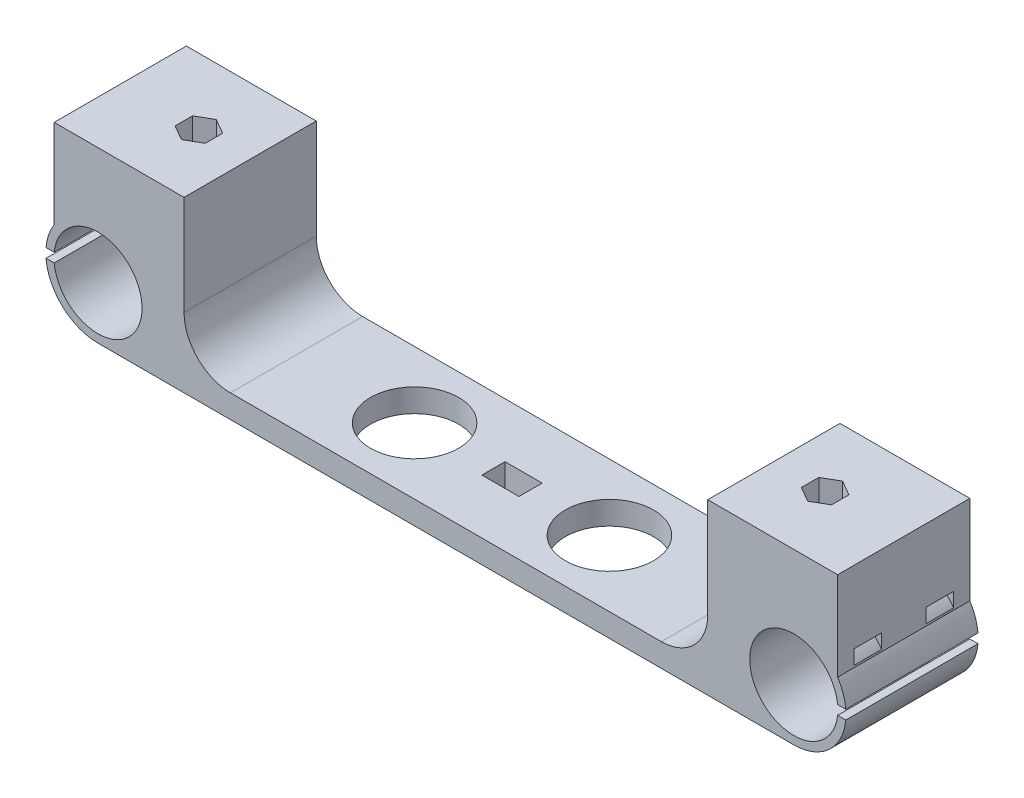
SolidWorks part; units mm, degrees
ref_plane "Front Plane" through (0, 0, 0) normal (0, 0, 1) x (1, 0, 0)
ref_plane "Top Plane" through (0, 0, 0) normal (0, 1, 0) x (1, 0, 0)
ref_plane "Right Plane" through (0, 0, 0) normal (1, 0, 0) x (0, 0, -1)
sketch "Sketch7" plane through (0, 0, 0) normal (0, 0, 1) x (1, 0, 0)
  line L0 (-35.0092, -3.4353) -> (114.9908, -3.4353)
  line L1 (-16.4565, 1.5647) -> (96.438, 1.5647)
  line L8 (126.1962, 6.8147) -> (124.438, 6.8147)
  line L9 (126.1962, 8.8147) -> (124.438, 8.8147)
  line L10 (39.9908, -3.4353) -> (39.9908, 54.826) construction
  line L11 (-46.2147, 8.8147) -> (-44.4565, 8.8147)
  line L12 (-46.2147, 6.8147) -> (-44.4565, 6.8147)
  line L19 (-44.4565, 13.9231) -> (-44.4565, 33.0647)
  line L20 (-44.4565, 33.0647) -> (-16.4565, 33.0647)
  line L21 (-16.4565, 33.0647) -> (-16.4565, 1.5647)
  line L22 (96.438, 33.0647) -> (96.438, 1.5647)
  line L23 (124.438, 13.9231) -> (124.438, 33.0647)
  line L24 (124.438, 33.0647) -> (96.438, 33.0647)
  arc A0 (124.438, 8.8147) -> (124.438, 6.8147) centre (114.9908, 7.8147) ccw
  arc A1 (-44.4565, 6.8147) -> (-44.4565, 8.8147) centre (-35.0092, 7.8147) ccw
  arc A2 (114.9908, -3.4353) -> (126.1962, 6.8147) centre (114.9908, 7.8147) ccw
  arc A3 (-44.4565, 13.9231) -> (-46.2147, 8.8147) centre (-35.0092, 7.8147) ccw
  arc A4 (-46.2147, 6.8147) -> (-35.0092, -3.4353) centre (-35.0092, 7.8147) ccw
  arc A5 (126.1962, 8.8147) -> (124.438, 13.9231) centre (114.9908, 7.8147) ccw
  dimension "D2" = 19
  dimension "D3" = 1.75
  dimension "D11" = 28
  dimension "D5" = 2
  dimension "D1" = 150
  dimension "D4" = 5
  dimension "D6" = 1
  dimension "D12" = 31.5
extrude "Boss-Extrude3" add sketch "Sketch7" along normal blind 28.5
fillet "Fillet1" radius 10 2 edges at (96.438, 1.5647, 14.25) (-16.4565, 1.5647, 14.25)
sketch "Sketch8" plane through (0, 1.5647, 0) normal (0, 1, 0) x (1, 0, 0)
  line L0 (39.9908, 0) -> (39.9908, -28.5) construction
  line L1 (86.438, 0) -> (-6.4565, 0) construction
  line L2 (86.438, -28.5) -> (-6.4565, -28.5) construction
  line L3 (86.438, -14.25) -> (-6.4565, -14.25) construction
  line L4 (35.9908, -11.75) -> (43.9908, -11.75)
  line L5 (35.9908, -11.75) -> (35.9908, -16.75)
  line L6 (35.9908, -16.75) -> (43.9908, -16.75)
  line L7 (43.9908, -11.75) -> (43.9908, -16.75)
  line L8 (86.438, -28.5) -> (86.438, 0) construction
  line L9 (-6.4565, 0) -> (-6.4565, -28.5) construction
  circle A0 centre (60.9908, -14.25) radius 9.5
  circle A1 centre (18.9908, -14.25) radius 9.5
  dimension "D5" = 19
  dimension "D7" = 21
  dimension "D1" = 5
  dimension "D2" = 8
  dimension "D3" = 4
  dimension "D4" = 2.5
  dimension "D6" = 21
extrude "Cut-Extrude4" cut sketch "Sketch8" against normal up to surface (5 mm away) up to face at (39.9908, -3.4353, 14.25)
sketch "Sketch10" plane through (0, 33.0647, 0) normal (0, 1, 0) x (1, 0, 0)
  line L0 (124.438, -14.25) -> (-44.4565, -14.25) construction
  line L1 (124.438, -28.5) -> (124.438, 0) construction
  line L2 (-44.4565, -28.5) -> (-44.4565, 0) construction
  line L3 (107.4908, 0) -> (107.4908, -28.5) construction
  line L4 (124.438, 0) -> (96.438, 0) construction
  line L5 (124.438, -28.5) -> (96.438, -28.5) construction
  line L6 (-27.5092, 0) -> (-27.5092, -28.5) construction
  line L7 (-16.4565, 0) -> (-44.4565, 0) construction
  line L8 (-16.4565, -28.5) -> (-44.4565, -28.5) construction
  line L9 (86.438, 0) -> (-6.4565, 0) construction
  circle A0 centre (107.4908, -14.25) radius 1.75
  circle A1 centre (-27.5092, -14.25) radius 1.75
  point P30 (39.9908, 0)
  dimension "D1" = 3.5
  dimension "D2" = 135
  dimension "D3" = 67.5
extrude "Cut-Extrude6" cut sketch "Sketch10" against normal blind 10
sketch "Sketch13" plane through (0, 33.0647, 0) normal (0, 1, 0) x (1, 0, 0)
  line L1 (104.2408, -12.3736) -> (104.2408, -16.1264)
  line L2 (104.2408, -16.1264) -> (107.4908, -18.0028)
  line L3 (107.4908, -18.0028) -> (110.7408, -16.1264)
  line L4 (110.7408, -16.1264) -> (110.7408, -12.3736)
  line L5 (110.7408, -12.3736) -> (107.4908, -10.4972)
  line L6 (107.4908, -10.4972) -> (104.2408, -12.3736)
  line L7 (-27.5092, -18.0028) -> (-24.2592, -16.1264)
  line L8 (-24.2592, -16.1264) -> (-24.2592, -12.3736)
  line L9 (-24.2592, -12.3736) -> (-27.5092, -10.4972)
  line L10 (-27.5092, -10.4972) -> (-30.7592, -12.3736)
  line L11 (-30.7592, -12.3736) -> (-30.7592, -16.1264)
  line L12 (-30.7592, -16.1264) -> (-27.5092, -18.0028)
  line L13 (126.1962, -28.5) -> (126.1962, 0) construction
  circle A0 centre (107.4908, -14.25) radius 3.25 construction
  circle A1 centre (-27.5092, -14.25) radius 3.25 construction
  dimension "D1" = 6.5
extrude "Cut-Extrude9" cut sketch "Sketch13" against normal blind 5
ref_axis "Axis2" through (114.9908, 7.8147, 28.5) along (0, 0, -1)
ref_plane "Plane1" through (114.9908, 0, 0) normal (-1, 0, 0) x (0, 0, 1)
sketch "Sketch17" plane through (114.9908, 0, 0) normal (-1, 0, 0) x (0, 0, 1)
  line L1 (25, 19.3147) -> (19, 19.3147)
  line L2 (25, 19.3147) -> (25, 21.3147)
  line L3 (25, 21.3147) -> (19, 21.3147)
  line L4 (19, 19.3147) -> (19, 21.3147)
  line L5 (28.5, 17.3147) -> (0, 17.3147) construction
  line L10 (28.5, 33.0647) -> (28.5, 13.9231) construction
  line L11 (3.5, 21.3147) -> (9.5, 21.3147)
  line L12 (3.5, 21.3147) -> (3.5, 19.3147)
  line L13 (3.5, 19.3147) -> (9.5, 19.3147)
  line L14 (9.5, 21.3147) -> (9.5, 19.3147)
  line L15 (0, 33.0647) -> (0, 13.9231) construction
  dimension "D1" = 2
  dimension "D3" = 2
  dimension "D4" = 6
  dimension "D5" = 3.5
  dimension "D6" = 3.5
revolve "Cut-Revolve1" cut sketch "Sketch17" angle 360 about axis through (114.9908, 7.8147, 28.5) along (0, 0, -1)
sketch "Sketch14" [suppressed] plane through (0, 0, 28) normal (0, 0, 1) x (1, 0, 0)
  line L1 (-82.4893, 23.5071) -> (44.7899, 150.7863)
  line L2 (-82.4893, 23.5071) -> (44.7899, -103.7721)
  line L3 (44.7899, -103.7721) -> (172.0692, 23.5071)
  line L4 (44.7899, 150.7863) -> (172.0692, 23.5071)
  line L6 (124.4774, 32.3147) -> (96.4774, 32.3147) construction
  dimension "D1" = 180
  dimension "D2" = 180
  dimension "D3" = 45
sketch "Sketch11" [suppressed] plane through (0, 0, 28.5) normal (0, 0, 1) x (1, 0, 0)
  line L1 (-81.97, 62.499) -> (96.4919, 62.499)
  line L2 (-81.97, 62.499) -> (-81.97, -13.3564)
  line L3 (-81.97, -13.3564) -> (96.4919, -13.3564)
  line L4 (96.4919, 62.499) -> (96.4919, -13.3564)
extrude "Cut-Extrude7" [suppressed] cut sketch "Sketch11" against normal blind 56
sketch "Sketch15" [suppressed] plane through (96.4919, 0, 0) normal (-1, 0, 0) x (0, 0, 1)
  line L1 (14.4804, 34.5927) -> (32.6535, 34.5927)
  line L2 (14.4804, 34.5927) -> (14.4804, -6.1058)
  line L3 (14.4804, -6.1058) -> (32.6535, -6.1058)
  line L4 (32.6535, 34.5927) -> (32.6535, -6.1058)
extrude "Cut-Extrude10" [suppressed] cut sketch "Sketch15" against normal blind 39
ref_plane "Plane2" through (39.9908, 0, 0) normal (1, 0, 0) x (0, 0, -1)
mirror "Mirror1" about plane through (39.9908, 0, 0) normal (1, 0, 0) of "Cut-Revolve1"
